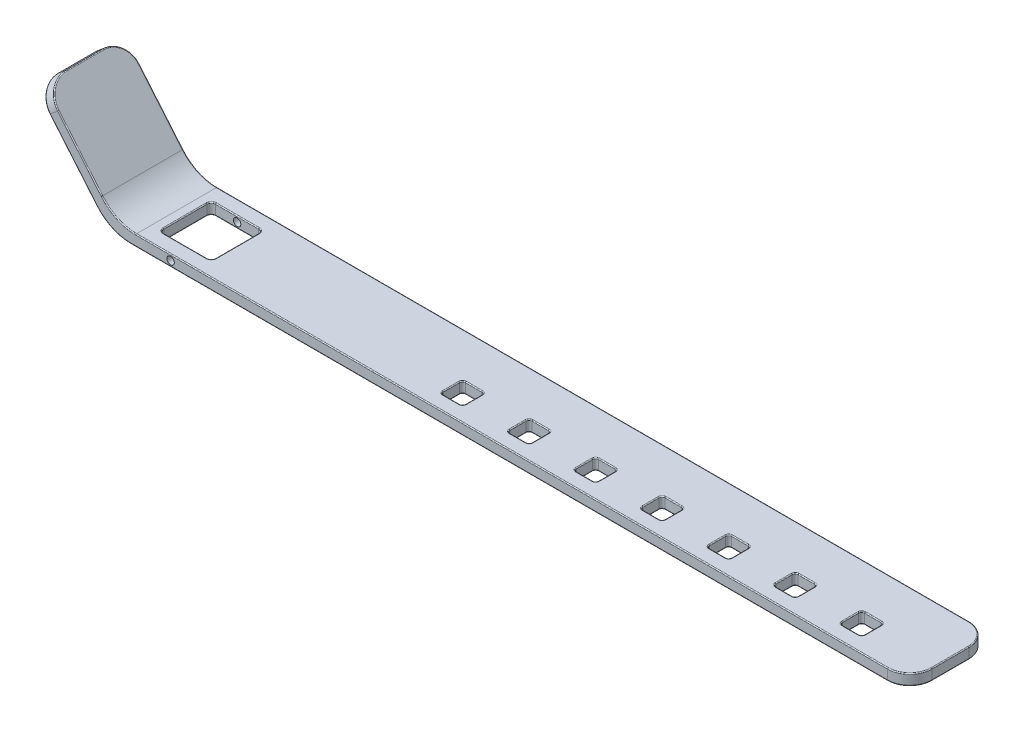
SolidWorks part; units mm, degrees
ref_plane "Front Plane" through (0, 0, 0) normal (0, 0, 1) x (1, 0, 0)
ref_plane "Top Plane" through (0, 0, 0) normal (0, 1, 0) x (1, 0, 0)
ref_plane "Right Plane" through (0, 0, 0) normal (1, 0, 0) x (0, 0, -1)
sketch "Sketch1" plane through (0, 0, 0) normal (0, 0, 1) x (1, 0, 0)
  line L0 (-98.5968, 5.7865) -> (-114.2836, 24.4813)
  line L1 (-89.4043, 1.5) -> (120, 1.5)
  line L3 (-90.8032, -1.5) -> (120, -1.5)
  line L4 (120, 1.5) -> (120, -1.5)
  line L5 (-114.2836, 24.4813) -> (-116.5818, 22.553)
  line L6 (-116.5818, 22.553) -> (-99.9958, 2.7865)
  circle A0 centre (-80, 0) radius 1
  arc A1 (-89.4043, 1.5) -> (-98.5968, 5.7865) centre (-89.4043, 13.5) cw
  arc A2 (-90.8032, -1.5) -> (-99.9958, 2.7865) centre (-90.8032, 10.5) cw
  point P4 (-80, 0)
  point P12 (-95, 1.5)
  dimension "D7" = 2
  dimension "D2" = 12
  dimension "D12" = 12
  dimension "D1" = 215
  dimension "D3" = 1.5
  dimension "D4" = 120
  dimension "D5" = 1.5
  dimension "D6" = 200
  dimension "D8" = 130
  dimension "D9" = 30
  dimension "D10" = 3
  dimension "D11" = 90
extrude "Boss-Extrude1" add sketch "Sketch1" along normal blind 11 and the other way blind 11
fillet "Fillet1" radius 6 4 edges at (-115.4327, 23.5172, -11) (-115.4327, 23.5172, 11) (120, 0, 11) (120, 0, -11)
sketch "Sketch2" plane through (0, 1.5, 0) normal (0, 1, 0) x (1, 0, 0)
  line L0 (114, -11) -> (-89.4043, -11) construction
  line L1 (-85.8, 7) -> (-74.2, 7)
  line L2 (-87, 5.8) -> (-87, -5.8)
  line L3 (-85.8, -7) -> (-74.2, -7)
  line L4 (-73, 5.8) -> (-73, -5.8)
  line L5 (120, 5) -> (120, -5) construction
  line L6 (79.8, -1) -> (84.2, -1)
  line L7 (97.8, -1) -> (102.2, -1)
  line L8 (97, -1.8) -> (97, -6.2)
  line L9 (97.8, -7) -> (102.2, -7)
  line L10 (103, -1.8) -> (103, -6.2)
  line L11 (85, -1.8) -> (85, -6.2)
  line L12 (79.8, -7) -> (84.2, -7)
  line L13 (79, -1.8) -> (79, -6.2)
  line L14 (61.8, -1) -> (66.2, -1)
  line L15 (67, -1.8) -> (67, -6.2)
  line L16 (61.8, -7) -> (66.2, -7)
  line L17 (61, -1.8) -> (61, -6.2)
  line L18 (43.8, -1) -> (48.2, -1)
  line L19 (49, -1.8) -> (49, -6.2)
  line L20 (43.8, -7) -> (48.2, -7)
  line L21 (43, -1.8) -> (43, -6.2)
  line L22 (25.8, -1) -> (30.2, -1)
  line L23 (31, -1.8) -> (31, -6.2)
  line L24 (25.8, -7) -> (30.2, -7)
  line L25 (25, -1.8) -> (25, -6.2)
  line L26 (7.8, -1) -> (12.2, -1)
  line L27 (13, -1.8) -> (13, -6.2)
  line L28 (7.8, -7) -> (12.2, -7)
  line L29 (7, -1.8) -> (7, -6.2)
  line L30 (-10.2, -1) -> (-5.8, -1)
  line L31 (-5, -1.8) -> (-5, -6.2)
  line L32 (-10.2, -7) -> (-5.8, -7)
  line L33 (-11, -1.8) -> (-11, -6.2)
  arc A0 (-85.8, -7) -> (-87, -5.8) centre (-85.8, -5.8) cw
  arc A1 (-74.2, -7) -> (-73, -5.8) centre (-74.2, -5.8) ccw
  arc A2 (-73, 5.8) -> (-74.2, 7) centre (-74.2, 5.8) ccw
  arc A3 (-85.8, 7) -> (-87, 5.8) centre (-85.8, 5.8) ccw
  arc A4 (103, -1.8) -> (102.2, -1) centre (102.2, -1.8) ccw
  arc A5 (103, -6.2) -> (102.2, -7) centre (102.2, -6.2) cw
  arc A6 (97.8, -7) -> (97, -6.2) centre (97.8, -6.2) cw
  arc A7 (97, -1.8) -> (97.8, -1) centre (97.8, -1.8) cw
  arc A8 (85, -1.8) -> (84.2, -1) centre (84.2, -1.8) ccw
  arc A9 (85, -6.2) -> (84.2, -7) centre (84.2, -6.2) cw
  arc A10 (79.8, -7) -> (79, -6.2) centre (79.8, -6.2) cw
  arc A11 (79, -1.8) -> (79.8, -1) centre (79.8, -1.8) cw
  arc A12 (67, -1.8) -> (66.2, -1) centre (66.2, -1.8) ccw
  arc A13 (67, -6.2) -> (66.2, -7) centre (66.2, -6.2) cw
  arc A14 (61.8, -7) -> (61, -6.2) centre (61.8, -6.2) cw
  arc A15 (61, -1.8) -> (61.8, -1) centre (61.8, -1.8) cw
  arc A16 (49, -1.8) -> (48.2, -1) centre (48.2, -1.8) ccw
  arc A17 (49, -6.2) -> (48.2, -7) centre (48.2, -6.2) cw
  arc A18 (43.8, -7) -> (43, -6.2) centre (43.8, -6.2) cw
  arc A19 (43, -1.8) -> (43.8, -1) centre (43.8, -1.8) cw
  arc A20 (31, -1.8) -> (30.2, -1) centre (30.2, -1.8) ccw
  arc A21 (31, -6.2) -> (30.2, -7) centre (30.2, -6.2) cw
  arc A22 (25.8, -7) -> (25, -6.2) centre (25.8, -6.2) cw
  arc A23 (25, -1.8) -> (25.8, -1) centre (25.8, -1.8) cw
  arc A24 (13, -1.8) -> (12.2, -1) centre (12.2, -1.8) ccw
  arc A25 (13, -6.2) -> (12.2, -7) centre (12.2, -6.2) cw
  arc A26 (7.8, -7) -> (7, -6.2) centre (7.8, -6.2) cw
  arc A27 (7, -1.8) -> (7.8, -1) centre (7.8, -1.8) cw
  arc A28 (-5, -1.8) -> (-5.8, -1) centre (-5.8, -1.8) ccw
  arc A29 (-5, -6.2) -> (-5.8, -7) centre (-5.8, -6.2) cw
  arc A30 (-10.2, -7) -> (-11, -6.2) centre (-10.2, -6.2) cw
  arc A31 (-11, -1.8) -> (-10.2, -1) centre (-10.2, -1.8) cw
  point P12 (-73, -7)
  point P15 (-73, 7)
  point P18 (-87, 7)
  point P23 (100, -7)
  point P26 (103, -1)
  point P31 (97, -7)
  point P34 (97, -1)
  dimension "D5" = 1.2
  dimension "D10" = 0.8
  dimension "D1" = 14
  dimension "D2" = 14
  dimension "D3" = 4
  dimension "D4" = 193
  dimension "D6" = 6
  dimension "D7" = 6
  dimension "D8" = 17
  dimension "D9" = 4
  dimension "D12" = 12
  dimension "D11" = 7
extrude "Cut-Extrude1" cut sketch "Sketch2" against normal up to next
fillet "Fillet2" radius 0.25 152 edges at (-95.8747, -0.3757, -11) (-95.8747, -0.3757, 11) (-94.4757, 2.6243, -11) (-94.4757, 2.6243, 11) (-115.4522, 21.2068, 9.2426) (-106.3604, 10.3716, 11) (-106.3604, 10.3716, -11) (-115.4522, 21.2068, -9.2426) (-116.5818, 22.553, 0) (-104.5119, 12.8358, 11) (-113.154, 23.1351, 9.2426) (-114.2836, 24.4813, 0) (-113.154, 23.1351, -9.2426) (-104.5119, 12.8358, -11) (-86.6485, -1.5, -6.6485) (-80, -1.5, -7) (-73.3515, -1.5, -6.6485) (-73, -1.5, 0) (-73.3515, -1.5, 6.6485) (-80, -1.5, 7) (-86.6485, -1.5, 6.6485) (-87, -1.5, 0) (118.2426, -1.5, -9.2426) (11.5984, -1.5, -11) (11.5984, -1.5, 11) (118.2426, -1.5, 9.2426) (120, -1.5, 0) (-5, -1.5, 4) (-5.2343, -1.5, 6.7657) (-8, -1.5, 7) (-10.7657, -1.5, 6.7657) (-11, -1.5, 4) (-10.7657, -1.5, 1.2343) (-8, -1.5, 1) (-5.2343, -1.5, 1.2343) (13, -1.5, 4) (12.7657, -1.5, 6.7657) (10, -1.5, 7) (7.2343, -1.5, 6.7657) (7, -1.5, 4) (7.2343, -1.5, 1.2343) (10, -1.5, 1) (12.7657, -1.5, 1.2343) (31, -1.5, 4) (30.7657, -1.5, 6.7657) (28, -1.5, 7) (25.2343, -1.5, 6.7657) (25, -1.5, 4) (25.2343, -1.5, 1.2343) (28, -1.5, 1) (30.7657, -1.5, 1.2343) (49, -1.5, 4) (48.7657, -1.5, 6.7657) (46, -1.5, 7) (43.2343, -1.5, 6.7657) (43, -1.5, 4) (43.2343, -1.5, 1.2343) (46, -1.5, 1) (48.7657, -1.5, 1.2343) (67, -1.5, 4) (66.7657, -1.5, 6.7657) (64, -1.5, 7) (61.2343, -1.5, 6.7657) (61, -1.5, 4) (61.2343, -1.5, 1.2343) (64, -1.5, 1) (66.7657, -1.5, 1.2343) (85, -1.5, 4) (84.7657, -1.5, 6.7657) (82, -1.5, 7) (79.2343, -1.5, 6.7657) (79, -1.5, 4) (79.2343, -1.5, 1.2343) (82, -1.5, 1) (84.7657, -1.5, 1.2343) (103, -1.5, 4) (102.7657, -1.5, 6.7657) (100, -1.5, 7) (97.2343, -1.5, 6.7657) (97, -1.5, 4) (97.2343, -1.5, 1.2343) (100, -1.5, 1) (102.7657, -1.5, 1.2343) (12.2978, 1.5, -11) (118.2426, 1.5, -9.2426) (120, 1.5, 0) (118.2426, 1.5, 9.2426) (12.2978, 1.5, 11) (-8, 1.5, 1) (-10.7657, 1.5, 1.2343) (-11, 1.5, 4) (-10.7657, 1.5, 6.7657) (-8, 1.5, 7) (-5.2343, 1.5, 6.7657) (-5, 1.5, 4) (-5.2343, 1.5, 1.2343) (10, 1.5, 1) (7.2343, 1.5, 1.2343) (7, 1.5, 4) (7.2343, 1.5, 6.7657) (10, 1.5, 7) (12.7657, 1.5, 6.7657) (13, 1.5, 4) (12.7657, 1.5, 1.2343) (28, 1.5, 1) (25.2343, 1.5, 1.2343) (25, 1.5, 4) (25.2343, 1.5, 6.7657) (28, 1.5, 7) (30.7657, 1.5, 6.7657) (31, 1.5, 4) (30.7657, 1.5, 1.2343) (46, 1.5, 1) (43.2343, 1.5, 1.2343) (43, 1.5, 4) (43.2343, 1.5, 6.7657) (46, 1.5, 7) (48.7657, 1.5, 6.7657) (49, 1.5, 4) (48.7657, 1.5, 1.2343) (64, 1.5, 1) (61.2343, 1.5, 1.2343) (61, 1.5, 4) (61.2343, 1.5, 6.7657) (64, 1.5, 7) (66.7657, 1.5, 6.7657) (67, 1.5, 4) (66.7657, 1.5, 1.2343) (82, 1.5, 1) (79.2343, 1.5, 1.2343) (79, 1.5, 4) (79.2343, 1.5, 6.7657) (82, 1.5, 7) (84.7657, 1.5, 6.7657) (85, 1.5, 4) (84.7657, 1.5, 1.2343) (100, 1.5, 1) (97.2343, 1.5, 1.2343) (97, 1.5, 4) (97.2343, 1.5, 6.7657) (100, 1.5, 7) (102.7657, 1.5, 6.7657) (103, 1.5, 4) (102.7657, 1.5, 1.2343) (-80, 1.5, 7) (-73.3515, 1.5, 6.6485) (-73, 1.5, 0) (-73.3515, 1.5, -6.6485) (-80, 1.5, -7) (-86.6485, 1.5, -6.6485) (-87, 1.5, 0) (-86.6485, 1.5, 6.6485)
